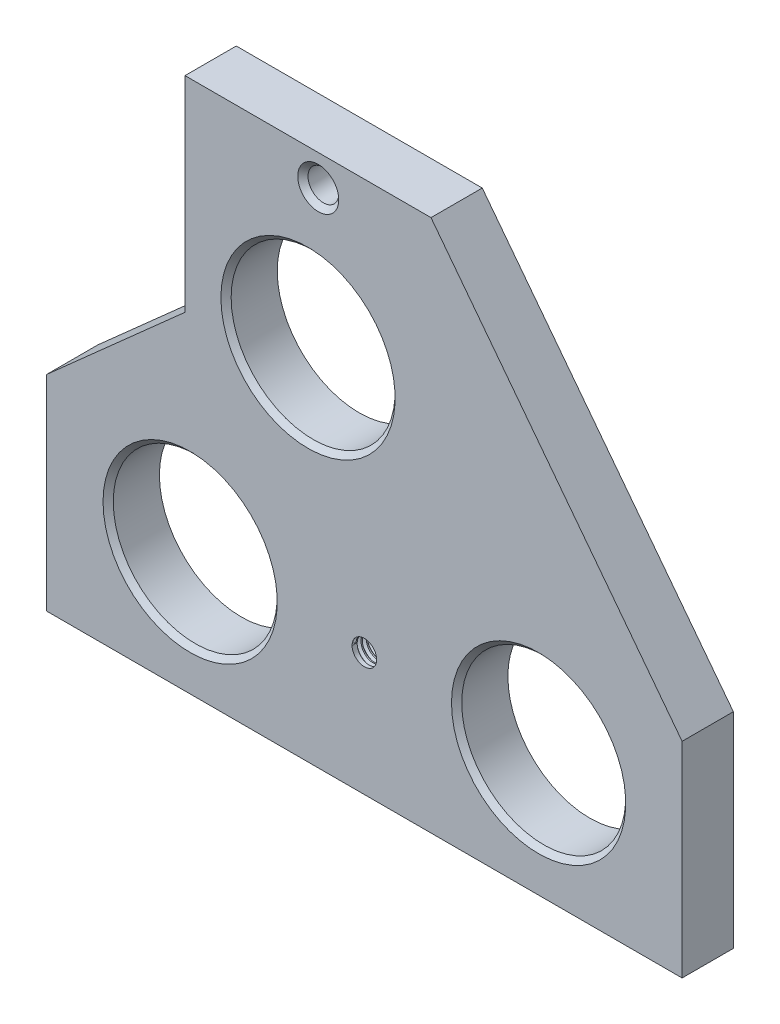
SolidWorks part; units mm, degrees
material "Stop 1060"
ref_plane "Płaszczyzna przednia" through (0, 0, 0) normal (0, 0, 1) x (1, 0, 0)
ref_plane "Płaszczyzna górna" through (0, 0, 0) normal (0, 1, 0) x (1, 0, 0)
ref_plane "Płaszczyzna prawa" through (0, 0, 0) normal (1, 0, 0) x (0, 0, -1)
sketch "Szkic1" plane through (0, 0, 0) normal (0, 0, 1) x (1, 0, 0)
  line L0 (-14, -12) -> (-14, 8)
  line L1 (-0.5, 40) -> (23.5, 40)
  line L2 (48, 8) -> (48, -12)
  line L3 (48, -12) -> (-14, -12)
  line L4 (-0.5, 40) -> (-0.5, 20)
  line L6 (-14, 8) -> (-0.5, 20)
  line L7 (23.5, 40) -> (48, 8)
  circle A0 centre (0, 0) radius 8
  circle A1 centre (34, 0) radius 8
  circle A2 centre (11.5, 23) radius 8
  circle A3 centre (12.5, 37) radius 1.5
  circle A4 centre (17, 0) radius 1.2
  dimension "D1" = 16
  dimension "D2" = 16
  dimension "D3" = 16
  dimension "D4" = 34
  dimension "D5" = 23
  dimension "D6" = 11.5
  dimension "D8" = 14
  dimension "D9" = 14
  dimension "D10" = 3
  dimension "D11" = 12
  dimension "D17" = 3
  dimension "D18" = 13
  dimension "D19" = 3
  dimension "D20" = 17
  dimension "D21" = 23
  dimension "D22" = 2.4
  dimension "D7" = 12
  dimension "D12" = 20
  dimension "D13" = 12
  dimension "D14" = 20
  dimension "D15" = 20
  dimension "D16" = 24
extrude "Dodanie-wyciągnięcie1" add sketch "Szkic1" along normal blind 5
chamfer "Sfazowanie2" distance 0.5 angle 45 4 edges at (42, 0, 5) (19.5, 23, 5) (8, 0, 5) (14, 37, 5)
thread "Gwint1" pitch 0.5 method cut profile "Profil gwintu1" start angle 0, offset 0, length 10, pitch 0.5, diameter 2.4
ref_plane "Płaszczyzna1" through (15.8, 0, 5) normal (0, -1, 0) x (-1, 0, 0)
sketch "Profil gwintu1" plane through (15.8, 0, 5) normal (0, -1, 0) x (-1, 0, 0)
  line L0 (0, 0) -> (0, 0.5) construction
  line L1 (0, 0) -> (0.2706, 0.1562)
  line L2 (0.2706, 0.1562) -> (0.2706, 0.2187)
  line L3 (0.2706, 0.2187) -> (0, 0.375)
  line L4 (0.2706, 0.1875) -> (0, 0.1875) construction
  line L11 (0, 0) -> (0, 0.375)
  point P2 (0, 0)
  dimension "Pitch" = 0.5
  dimension "Profile_Angle" = 60
  dimension "Profile_Land" = 0.0625
  dimension "Profile_Height" = 0.2706
